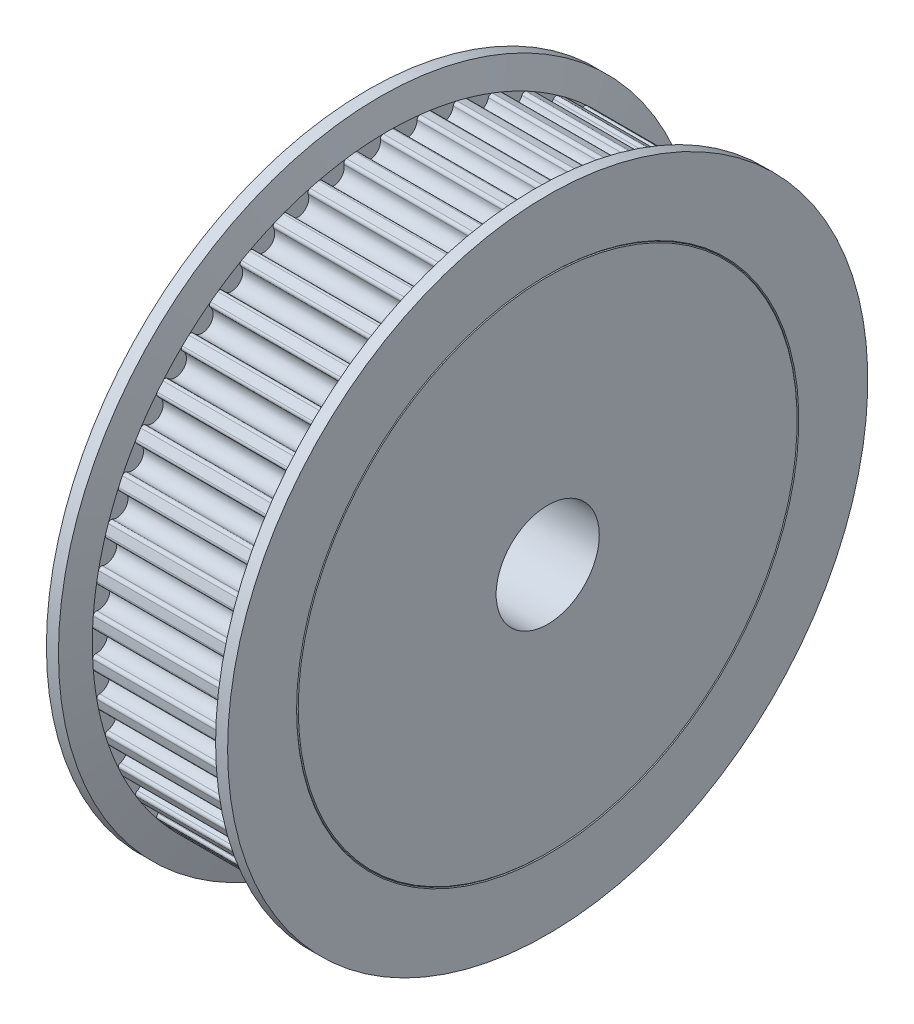
SolidWorks part; units mm, degrees
material "6061-O (SS)"
ref_plane "Сверху" through (0, 0, 0) normal (0, 0, 1) x (1, 0, 0)
ref_plane "Справа" through (0, 0, 0) normal (0, 1, 0) x (1, 0, 0)
ref_plane "Спереди" through (0, 0, 0) normal (1, 0, 0) x (0, 0, -1)
sketch "Эскиз1" plane through (0, 0, 0) normal (0, 0, 1) x (1, 0, 0)
  line L0 (0, 0) -> (0, 7.2824)
  line L1 (0, 7.2824) -> (0.2, 7.5)
  line L2 (0.2, 7.5) -> (6, 7.5)
  line L3 (14.9588, 12.5217) -> (5.3685, 12.5217) construction
  line L4 (7, 14.78) -> (14, 14.78)
  line L5 (6, 7.5) -> (6, 12.4805)
  line L6 (14.3982, 16.0142) -> (15, 16.0142)
  line L7 (15, 0) -> (15, 12.4805)
  line L8 (15, 12.4805) -> (14.9588, 12.5217)
  line L9 (14.9588, 12.5217) -> (15, 12.5629)
  line L10 (15, 12.5629) -> (15, 16.0142)
  line L11 (0, 0) -> (15, 0)
  line L12 (6, 16.0796) -> (6.6018, 16.0796)
  line L13 (14, 14.78) -> (14.3982, 16.0142)
  line L14 (6.6018, 16.0796) -> (7, 14.78)
  line L15 (6, 12.4805) -> (6.0412, 12.5217)
  line L16 (6.0412, 12.5217) -> (6, 12.5629)
  line L17 (6, 12.5629) -> (6, 16.0796)
  dimension "D1" = 1
  dimension "D2" = 5.8
  dimension "D3" = 7.5
  dimension "D4" = 15
  dimension "D5" = 1
  dimension "D6" = 14.78
  dimension "D8" = 7
revolve "Body" add sketch "Эскиз1" angle 360 about L11 region at (8.3609, 5.544, 0) region at (10.4904, 13.8062, 0)
sketch "Эскиз2" plane through (15, 0, 0) normal (1, 0, 0) x (0, 0, -1)
  circle A0 centre (0, 0) radius 2.58
  dimension "D1" = 5.16
extrude "Bore" cut sketch "Эскиз2" against normal through all
sketch "Эскиз3" plane through (6, 0, 0) normal (-1, 0, 0) x (0, 0, 1)
  line L0 (0, 0) -> (9.7637, 0) construction
  circle A0 centre (14.4574, -1.8264) radius 0.55
  circle A1 centre (-11.7892, -8.5654) radius 0.55
  circle A2 centre (14.1144, -3.624) radius 0.55
  circle A3 centre (13.5489, -5.3644) radius 0.55
  circle A4 centre (12.7698, -7.0202) radius 0.55
  circle A5 centre (11.7892, -8.5654) radius 0.55
  circle A6 centre (14.5723, 0) radius 0.55
  circle A7 centre (10.6227, -9.9754) radius 0.55
  circle A8 centre (9.2887, -11.2281) radius 0.55
  circle A9 centre (7.8082, -12.3038) radius 0.55
  circle A10 centre (6.2046, -13.1854) radius 0.55
  circle A11 centre (4.5031, -13.859) radius 0.55
  circle A12 centre (2.7306, -14.3141) radius 0.55
  circle A13 centre (0.915, -14.5435) radius 0.55
  circle A14 centre (-0.915, -14.5435) radius 0.55
  circle A15 centre (-12.7698, -7.0202) radius 0.55
  circle A16 centre (-13.5489, -5.3644) radius 0.55
  circle A17 centre (-2.7306, -14.3141) radius 0.55
  circle A18 centre (-4.5031, -13.859) radius 0.55
  circle A19 centre (-6.2046, -13.1854) radius 0.55
  circle A20 centre (-7.8082, -12.3038) radius 0.55
  circle A21 centre (-9.2887, -11.2281) radius 0.55
  circle A22 centre (-10.6227, -9.9754) radius 0.55
  circle A23 centre (-14.1144, -3.624) radius 0.55
  circle A24 centre (-14.4574, -1.8264) radius 0.55
  circle A25 centre (-14.5723, 0) radius 0.55
  circle A26 centre (-14.4574, 1.8264) radius 0.55
  circle A27 centre (-14.1144, 3.624) radius 0.55
  circle A28 centre (-13.5489, 5.3644) radius 0.55
  circle A29 centre (-12.7698, 7.0202) radius 0.55
  circle A30 centre (-11.7892, 8.5654) radius 0.55
  circle A31 centre (-10.6227, 9.9754) radius 0.55
  circle A32 centre (-9.2887, 11.2281) radius 0.55
  circle A33 centre (-7.8082, 12.3038) radius 0.55
  circle A34 centre (-6.2046, 13.1854) radius 0.55
  circle A35 centre (-4.5031, 13.859) radius 0.55
  circle A36 centre (-2.7306, 14.3141) radius 0.55
  circle A37 centre (-0.915, 14.5435) radius 0.55
  circle A38 centre (0.915, 14.5435) radius 0.55
  circle A39 centre (2.7306, 14.3141) radius 0.55
  circle A40 centre (4.5031, 13.859) radius 0.55
  circle A41 centre (6.2046, 13.1854) radius 0.55
  circle A42 centre (7.8082, 12.3038) radius 0.55
  circle A43 centre (9.2887, 11.2281) radius 0.55
  circle A44 centre (10.6227, 9.9754) radius 0.55
  circle A45 centre (11.7892, 8.5654) radius 0.55
  circle A46 centre (12.7698, 7.0202) radius 0.55
  circle A47 centre (13.5489, 5.3644) radius 0.55
  circle A48 centre (14.1144, 3.624) radius 0.55
  circle A49 centre (14.4574, 1.8264) radius 0.55
  point P45 (0, 0)
  dimension "D1" = 50
  dimension "D2" = 1.83
extrude "20tooth" cut sketch "Эскиз3" against normal blind 7 from offset 1 offset against normal yes
fillet "Скругление1" radius 0.15 100 edges at (10.5, 0.5128, 14.7711) (10.5, -0.5128, 14.7711) (10.5, -2.3601, 14.5904) (10.5, -1.3426, 14.7189) (10.5, -4.1701, 14.1795) (10.5, -3.1767, 14.4346) (10.5, -5.9144, 13.545) (10.5, -4.9608, 13.9226) (10.5, -7.5654, 12.697) (10.5, -6.6667, 13.1911) (10.5, -9.0971, 11.6487) (10.5, -8.2674, 12.2515) (10.5, -10.4853, 10.4166) (10.5, -9.7377, 11.1187) (10.5, -11.7082, 9.0203) (10.5, -11.0545, 9.8106) (10.5, -12.7464, 7.4818) (10.5, -12.1969, 8.3477) (10.5, -13.5836, 5.8252) (10.5, -13.147, 6.7532) (10.5, -14.2066, 4.0768) (10.5, -13.8897, 5.0522) (10.5, -14.6056, 2.2641) (10.5, -14.4134, 3.2715) (10.5, -14.7742, 0.4157) (10.5, -14.7098, 1.4393) (10.5, -14.7098, -1.4393) (10.5, -14.7742, -0.4157) (10.5, -14.4134, -3.2715) (10.5, -14.6056, -2.2641) (10.5, -14.2066, -4.0768) (10.5, -13.5836, -5.8252) (10.5, -12.7464, -7.4818) (10.5, -11.7082, -9.0203) (10.5, -10.4853, -10.4166) (10.5, -9.7377, -11.1187) (10.5, -11.0545, -9.8106) (10.5, -13.8897, -5.0522) (10.5, -13.147, -6.7532) (10.5, -12.1969, -8.3477) (10.5, -4.1701, -14.1795) (10.5, -4.9608, -13.9226) (10.5, -5.9144, -13.545) (10.5, -6.6667, -13.1911) (10.5, -7.5654, -12.697) (10.5, -8.2674, -12.2515) (10.5, -9.0971, -11.6487) (10.5, -3.1767, -14.4346) (10.5, -2.3601, -14.5904) (10.5, -1.3426, -14.7189) (10.5, -0.5128, -14.7711) (10.5, 0.5128, -14.7711) (10.5, 1.3426, -14.7189) (10.5, 2.3601, -14.5904) (10.5, 3.1767, -14.4346) (10.5, 4.1701, -14.1795) (10.5, 4.9608, -13.9226) (10.5, 5.9144, -13.545) (10.5, 6.6667, -13.1911) (10.5, 7.5654, -12.697) (10.5, 8.2674, -12.2515) (10.5, 9.0971, -11.6487) (10.5, 9.7377, -11.1187) (10.5, 10.4853, -10.4166) (10.5, 11.0545, -9.8106) (10.5, 11.7082, -9.0203) (10.5, 12.1969, -8.3477) (10.5, 12.7464, -7.4818) (10.5, 13.147, -6.7532) (10.5, 13.5836, -5.8252) (10.5, 13.8897, -5.0522) (10.5, 14.2066, -4.0768) (10.5, 14.4134, -3.2715) (10.5, 14.6056, -2.2641) (10.5, 14.7098, -1.4393) (10.5, 14.7742, -0.4157) (10.5, 14.7742, 0.4157) (10.5, 14.7098, 1.4393) (10.5, 14.6056, 2.2641) (10.5, 14.4134, 3.2715) (10.5, 14.2066, 4.0768) (10.5, 13.8897, 5.0522) (10.5, 13.5836, 5.8252) (10.5, 13.147, 6.7532) (10.5, 12.7464, 7.4818) (10.5, 12.1969, 8.3477) (10.5, 11.7082, 9.0203) (10.5, 11.0545, 9.8106) (10.5, 10.4853, 10.4166) (10.5, 9.7377, 11.1187) (10.5, 9.0971, 11.6487) (10.5, 8.2674, 12.2515) (10.5, 7.5654, 12.697) (10.5, 6.6667, 13.1911) (10.5, 5.9144, 13.545) (10.5, 4.9608, 13.9226) (10.5, 4.1701, 14.1795) (10.5, 3.1767, 14.4346) (10.5, 2.3601, 14.5904) (10.5, 1.3426, 14.7189)
